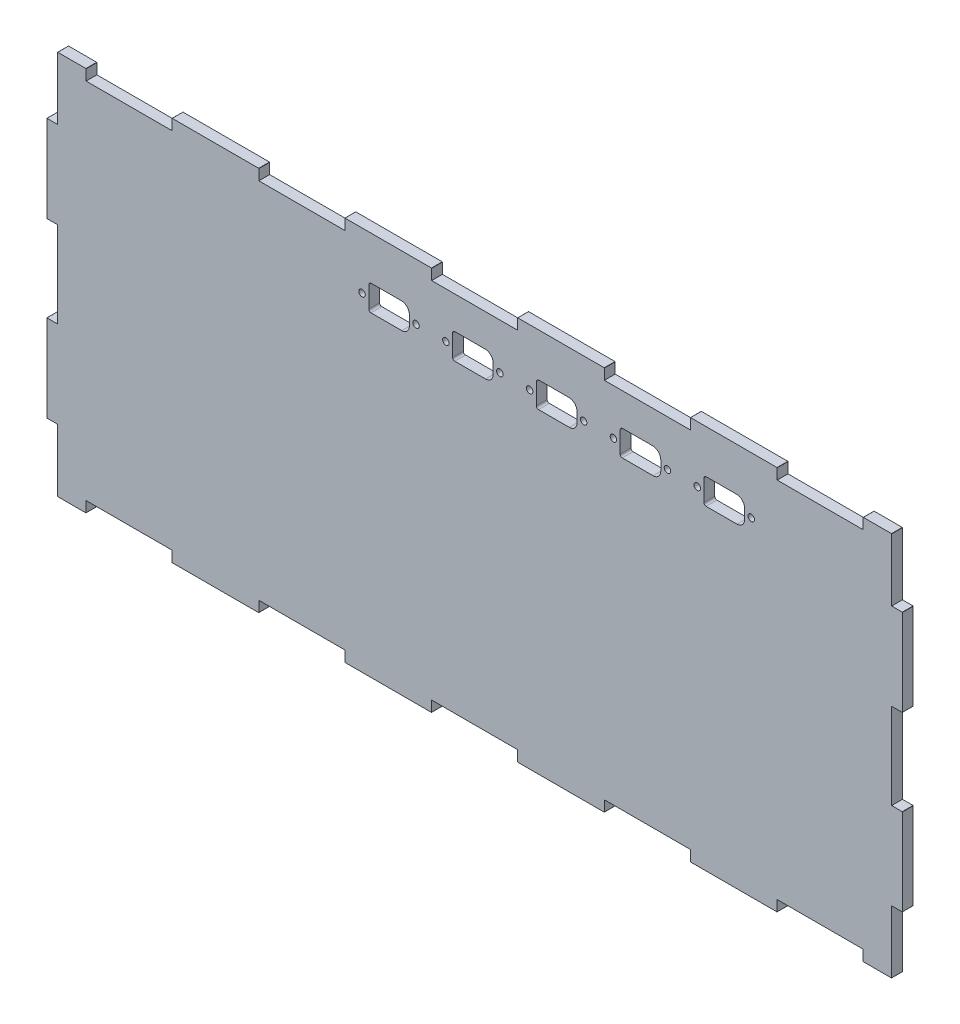
SolidWorks part; units mm, degrees
material "Acrylic (Medium-high impact)"
ref_plane "Front Plane" through (0, 0, 0) normal (0, 0, 1) x (1, 0, 0)
ref_plane "Top Plane" through (0, 0, 0) normal (0, 1, 0) x (1, 0, 0)
ref_plane "Right Plane" through (0, 0, 0) normal (1, 0, 0) x (0, 0, -1)
sketch "Model" plane through (0, 0, 0) normal (0, 0, 1) x (1, 0, 0)
  line L0 (-179.94, -89.08) -> (-179.93, -89.07)
  line L1 (-179.93, -89.07) -> (-179.92, -89.05)
  line L2 (-179.92, -89.05) -> (-179.91, -89.04)
  line L3 (-179.91, -89.04) -> (-179.9, -89.02)
  line L4 (-179.9, -89.02) -> (-179.9, -84.1)
  line L5 (-179.9, -84.1) -> (-140.1, -84.1)
  line L6 (-140.1, -84.1) -> (-140.1, -89.02)
  line L7 (-140.1, -89.02) -> (-140.08, -89.06)
  line L8 (-140.08, -89.06) -> (-140.07, -89.07)
  line L9 (-140.07, -89.07) -> (-140.05, -89.08)
  line L10 (-140.05, -89.08) -> (-140.04, -89.09)
  line L11 (-140.04, -89.09) -> (-140.02, -89.1)
  line L12 (-140.02, -89.1) -> (-99.98, -89.1)
  line L13 (-99.98, -89.1) -> (-99.94, -89.08)
  line L14 (-99.94, -89.08) -> (-99.93, -89.07)
  line L15 (-99.93, -89.07) -> (-99.92, -89.05)
  line L16 (-99.92, -89.05) -> (-99.91, -89.04)
  line L17 (-99.91, -89.04) -> (-99.9, -89.02)
  line L18 (-99.9, -89.02) -> (-99.9, -84.1)
  line L19 (-99.9, -84.1) -> (-60.1, -84.1)
  line L20 (-60.1, -84.1) -> (-60.1, -89.02)
  line L21 (-60.1, -89.02) -> (-60.08, -89.06)
  line L22 (-60.08, -89.06) -> (-60.07, -89.07)
  line L23 (-60.07, -89.07) -> (-60.05, -89.08)
  line L24 (-60.05, -89.08) -> (-60.04, -89.09)
  line L25 (-60.04, -89.09) -> (-60.02, -89.1)
  line L26 (-60.02, -89.1) -> (-19.98, -89.1)
  line L27 (-19.98, -89.1) -> (-19.94, -89.08)
  line L28 (-19.94, -89.08) -> (-19.93, -89.07)
  line L29 (-19.93, -89.07) -> (-19.92, -89.05)
  line L30 (-19.92, -89.05) -> (-19.91, -89.04)
  line L31 (-19.91, -89.04) -> (-19.9, -89.02)
  line L32 (-19.9, -89.02) -> (-19.9, -84.1)
  line L33 (-19.9, -84.1) -> (19.9, -84.1)
  line L34 (19.9, -84.1) -> (19.9, -89.02)
  line L35 (19.9, -89.02) -> (19.92, -89.06)
  line L36 (19.92, -89.06) -> (19.93, -89.07)
  line L37 (19.93, -89.07) -> (19.95, -89.08)
  line L38 (19.95, -89.08) -> (19.96, -89.09)
  line L39 (19.96, -89.09) -> (19.98, -89.1)
  line L40 (19.98, -89.1) -> (60.02, -89.1)
  line L41 (60.02, -89.1) -> (60.06, -89.08)
  line L42 (60.06, -89.08) -> (60.07, -89.07)
  line L43 (60.07, -89.07) -> (60.08, -89.05)
  line L44 (60.08, -89.05) -> (60.09, -89.04)
  line L45 (60.09, -89.04) -> (60.1, -89.02)
  line L46 (60.1, -89.02) -> (60.1, -84.1)
  line L47 (60.1, -84.1) -> (99.9, -84.1)
  line L48 (99.9, -84.1) -> (99.9, -89.02)
  line L49 (99.9, -89.02) -> (99.92, -89.06)
  line L50 (99.92, -89.06) -> (99.93, -89.07)
  line L51 (99.93, -89.07) -> (99.95, -89.08)
  line L52 (99.95, -89.08) -> (99.96, -89.09)
  line L53 (99.96, -89.09) -> (99.98, -89.1)
  line L54 (99.98, -89.1) -> (140.02, -89.1)
  line L55 (140.02, -89.1) -> (140.06, -89.08)
  line L56 (140.06, -89.08) -> (140.07, -89.07)
  line L57 (140.07, -89.07) -> (140.08, -89.05)
  line L58 (140.08, -89.05) -> (140.09, -89.04)
  line L59 (140.09, -89.04) -> (140.1, -89.02)
  line L60 (140.1, -89.02) -> (140.1, -84.1)
  line L61 (140.1, -84.1) -> (179.9, -84.1)
  line L62 (179.9, -84.1) -> (179.9, -89.02)
  line L63 (179.9, -89.02) -> (179.92, -89.06)
  line L64 (179.92, -89.06) -> (179.93, -89.07)
  line L65 (179.93, -89.07) -> (179.95, -89.08)
  line L66 (179.95, -89.08) -> (179.96, -89.09)
  line L67 (179.96, -89.09) -> (179.98, -89.1)
  line L68 (179.98, -89.1) -> (193.02, -89.1)
  line L69 (193.02, -89.1) -> (193.06, -89.08)
  line L70 (193.06, -89.08) -> (193.07, -89.07)
  line L71 (193.07, -89.07) -> (193.08, -89.05)
  line L72 (193.08, -89.05) -> (193.09, -89.04)
  line L73 (193.09, -89.04) -> (193.1, -89.02)
  line L74 (193.1, -89.02) -> (193.1, -60.1)
  line L75 (193.1, -60.1) -> (198.02, -60.1)
  line L76 (198.02, -60.1) -> (198.06, -60.08)
  line L77 (198.06, -60.08) -> (198.07, -60.07)
  line L78 (198.07, -60.07) -> (198.08, -60.05)
  line L79 (198.08, -60.05) -> (198.09, -60.04)
  line L80 (198.09, -60.04) -> (198.1, -60.02)
  line L81 (198.1, -60.02) -> (198.1, -19.98)
  line L82 (198.1, -19.98) -> (198.08, -19.94)
  line L83 (198.08, -19.94) -> (198.07, -19.93)
  line L84 (198.07, -19.93) -> (198.05, -19.92)
  line L85 (198.05, -19.92) -> (198.04, -19.91)
  line L86 (198.04, -19.91) -> (198.02, -19.9)
  line L87 (198.02, -19.9) -> (193.1, -19.9)
  line L88 (193.1, -19.9) -> (193.1, 19.9)
  line L89 (193.1, 19.9) -> (198.02, 19.9)
  line L90 (198.02, 19.9) -> (198.06, 19.92)
  line L91 (198.06, 19.92) -> (198.07, 19.93)
  line L92 (198.07, 19.93) -> (198.08, 19.95)
  line L93 (198.08, 19.95) -> (198.09, 19.96)
  line L94 (198.09, 19.96) -> (198.1, 19.98)
  line L95 (198.1, 19.98) -> (198.1, 60.02)
  line L96 (198.1, 60.02) -> (198.08, 60.06)
  line L97 (198.08, 60.06) -> (198.07, 60.07)
  line L98 (198.07, 60.07) -> (198.05, 60.08)
  line L99 (198.05, 60.08) -> (198.04, 60.09)
  line L100 (198.04, 60.09) -> (198.02, 60.1)
  line L101 (198.02, 60.1) -> (193.1, 60.1)
  line L102 (193.1, 60.1) -> (193.1, 89.02)
  line L103 (193.1, 89.02) -> (193.08, 89.06)
  line L104 (193.08, 89.06) -> (193.07, 89.07)
  line L105 (193.07, 89.07) -> (193.05, 89.08)
  line L106 (193.05, 89.08) -> (193.04, 89.09)
  line L107 (193.04, 89.09) -> (193.02, 89.1)
  line L108 (193.02, 89.1) -> (179.98, 89.1)
  line L109 (179.98, 89.1) -> (179.94, 89.08)
  line L110 (179.94, 89.08) -> (179.93, 89.07)
  line L111 (179.93, 89.07) -> (179.92, 89.05)
  line L112 (179.92, 89.05) -> (179.91, 89.04)
  line L113 (179.91, 89.04) -> (179.9, 89.02)
  line L114 (179.9, 89.02) -> (179.9, 84.1)
  line L115 (179.9, 84.1) -> (140.1, 84.1)
  line L116 (140.1, 84.1) -> (140.1, 89.02)
  line L117 (140.1, 89.02) -> (140.08, 89.06)
  line L118 (140.08, 89.06) -> (140.07, 89.07)
  line L119 (140.07, 89.07) -> (140.05, 89.08)
  line L120 (140.05, 89.08) -> (140.04, 89.09)
  line L121 (140.04, 89.09) -> (140.02, 89.1)
  line L122 (140.02, 89.1) -> (99.98, 89.1)
  line L123 (99.98, 89.1) -> (99.94, 89.08)
  line L124 (99.94, 89.08) -> (99.93, 89.07)
  line L125 (99.93, 89.07) -> (99.92, 89.05)
  line L126 (99.92, 89.05) -> (99.91, 89.04)
  line L127 (99.91, 89.04) -> (99.9, 89.02)
  line L128 (99.9, 89.02) -> (99.9, 84.1)
  line L129 (99.9, 84.1) -> (60.1, 84.1)
  line L130 (60.1, 84.1) -> (60.1, 89.02)
  line L131 (60.1, 89.02) -> (60.08, 89.06)
  line L132 (60.08, 89.06) -> (60.07, 89.07)
  line L133 (60.07, 89.07) -> (60.05, 89.08)
  line L134 (60.05, 89.08) -> (60.04, 89.09)
  line L135 (60.04, 89.09) -> (60.02, 89.1)
  line L136 (60.02, 89.1) -> (19.98, 89.1)
  line L137 (19.98, 89.1) -> (19.94, 89.08)
  line L138 (19.94, 89.08) -> (19.93, 89.07)
  line L139 (19.93, 89.07) -> (19.92, 89.05)
  line L140 (19.92, 89.05) -> (19.91, 89.04)
  line L141 (19.91, 89.04) -> (19.9, 89.02)
  line L142 (19.9, 89.02) -> (19.9, 84.1)
  line L143 (19.9, 84.1) -> (-19.9, 84.1)
  line L144 (-19.9, 84.1) -> (-19.9, 89.02)
  line L145 (-19.9, 89.02) -> (-19.92, 89.06)
  line L146 (-19.92, 89.06) -> (-19.93, 89.07)
  line L147 (-19.93, 89.07) -> (-19.95, 89.08)
  line L148 (-19.95, 89.08) -> (-19.96, 89.09)
  line L149 (-19.96, 89.09) -> (-19.98, 89.1)
  line L150 (-19.98, 89.1) -> (-60.02, 89.1)
  line L151 (-60.02, 89.1) -> (-60.06, 89.08)
  line L152 (-60.06, 89.08) -> (-60.07, 89.07)
  line L153 (-60.07, 89.07) -> (-60.08, 89.05)
  line L154 (-60.08, 89.05) -> (-60.09, 89.04)
  line L155 (-60.09, 89.04) -> (-60.1, 89.02)
  line L156 (-60.1, 89.02) -> (-60.1, 84.1)
  line L157 (-60.1, 84.1) -> (-99.9, 84.1)
  line L158 (-99.9, 84.1) -> (-99.9, 89.02)
  line L159 (-99.9, 89.02) -> (-99.92, 89.06)
  line L160 (-99.92, 89.06) -> (-99.93, 89.07)
  line L161 (-99.93, 89.07) -> (-99.95, 89.08)
  line L162 (-99.95, 89.08) -> (-99.96, 89.09)
  line L163 (-99.96, 89.09) -> (-99.98, 89.1)
  line L164 (-99.98, 89.1) -> (-140.02, 89.1)
  line L165 (-140.02, 89.1) -> (-140.06, 89.08)
  line L166 (-140.06, 89.08) -> (-140.07, 89.07)
  line L167 (-140.07, 89.07) -> (-140.08, 89.05)
  line L168 (-140.08, 89.05) -> (-140.09, 89.04)
  line L169 (-140.09, 89.04) -> (-140.1, 89.02)
  line L170 (-140.1, 89.02) -> (-140.1, 84.1)
  line L171 (-140.1, 84.1) -> (-179.9, 84.1)
  line L172 (-179.9, 84.1) -> (-179.9, 89.02)
  line L173 (-179.9, 89.02) -> (-179.92, 89.06)
  line L174 (-179.92, 89.06) -> (-179.93, 89.07)
  line L175 (-179.93, 89.07) -> (-179.95, 89.08)
  line L176 (-179.95, 89.08) -> (-179.96, 89.09)
  line L177 (-179.96, 89.09) -> (-179.98, 89.1)
  line L178 (-179.98, 89.1) -> (-193.02, 89.1)
  line L179 (-193.02, 89.1) -> (-193.06, 89.08)
  line L180 (-193.06, 89.08) -> (-193.07, 89.07)
  line L181 (-193.07, 89.07) -> (-193.08, 89.05)
  line L182 (-193.08, 89.05) -> (-193.09, 89.04)
  line L183 (-193.09, 89.04) -> (-193.1, 89.02)
  line L184 (-193.1, 89.02) -> (-193.1, 60.1)
  line L185 (-193.1, 60.1) -> (-198.02, 60.1)
  line L186 (-198.02, 60.1) -> (-198.06, 60.08)
  line L187 (-198.06, 60.08) -> (-198.07, 60.07)
  line L188 (-198.07, 60.07) -> (-198.08, 60.05)
  line L189 (-198.08, 60.05) -> (-198.09, 60.04)
  line L190 (-198.09, 60.04) -> (-198.1, 60.02)
  line L191 (-198.1, 60.02) -> (-198.1, 19.98)
  line L192 (-198.1, 19.98) -> (-198.08, 19.94)
  line L193 (-198.08, 19.94) -> (-198.07, 19.93)
  line L194 (-198.07, 19.93) -> (-198.05, 19.92)
  line L195 (-198.05, 19.92) -> (-198.04, 19.91)
  line L196 (-198.04, 19.91) -> (-198.02, 19.9)
  line L197 (-198.02, 19.9) -> (-193.1, 19.9)
  line L198 (-193.1, 19.9) -> (-193.1, -19.9)
  line L199 (-193.1, -19.9) -> (-198.02, -19.9)
  line L200 (-198.02, -19.9) -> (-198.06, -19.92)
  line L201 (-198.06, -19.92) -> (-198.07, -19.93)
  line L202 (-198.07, -19.93) -> (-198.08, -19.95)
  line L203 (-198.08, -19.95) -> (-198.09, -19.96)
  line L204 (-198.09, -19.96) -> (-198.1, -19.98)
  line L205 (-198.1, -19.98) -> (-198.1, -60.02)
  line L206 (-198.1, -60.02) -> (-198.08, -60.06)
  line L207 (-198.08, -60.06) -> (-198.07, -60.07)
  line L208 (-198.07, -60.07) -> (-198.05, -60.08)
  line L209 (-198.05, -60.08) -> (-198.04, -60.09)
  line L210 (-198.04, -60.09) -> (-198.02, -60.1)
  line L211 (-198.02, -60.1) -> (-193.1, -60.1)
  line L212 (-193.1, -60.1) -> (-193.1, -89.02)
  line L213 (-193.1, -89.02) -> (-193.08, -89.06)
  line L214 (-193.08, -89.06) -> (-193.07, -89.07)
  line L215 (-193.07, -89.07) -> (-193.05, -89.08)
  line L216 (-193.05, -89.08) -> (-193.04, -89.09)
  line L217 (-193.04, -89.09) -> (-193.02, -89.1)
  line L218 (-193.02, -89.1) -> (-179.98, -89.1)
  line L219 (-179.98, -89.1) -> (-179.94, -89.08)
extrude "Boss-Extrude1" add sketch "Model" along normal blind 5
sketch "Sketch2" plane through (0, 0, 5) normal (0, 0, 1) x (1, 0, 0)
  line L0 (-30.2088, 62.97) -> (-10.2088, 62.97) construction
  line L1 (-33.7338, 57.12) -> (-48.0088, 57.12)
  line L2 (-47.8088, 69.02) -> (-33.9338, 69.02)
  line L3 (-49.0088, 58.12) -> (-49.0088, 67.82)
  line L4 (-30.2088, 60.645) -> (-30.2088, 65.295)
  line L5 (5.0662, 57.12) -> (-9.2088, 57.12)
  line L6 (-9.0088, 69.02) -> (4.8662, 69.02)
  line L7 (-10.2088, 58.12) -> (-10.2088, 67.82)
  line L8 (8.5912, 60.645) -> (8.5912, 65.295)
  line L9 (43.8662, 57.12) -> (29.5912, 57.12)
  line L10 (29.7912, 69.02) -> (43.6662, 69.02)
  line L11 (28.5912, 58.12) -> (28.5912, 67.82)
  line L12 (47.3912, 60.645) -> (47.3912, 65.295)
  line L13 (82.6662, 57.12) -> (68.3912, 57.12)
  line L14 (68.5912, 69.02) -> (82.4662, 69.02)
  line L15 (67.3912, 58.12) -> (67.3912, 67.82)
  line L16 (86.1912, 60.645) -> (86.1912, 65.295)
  line L17 (8.5912, 62.97) -> (28.5912, 62.97) construction
  line L18 (47.3912, 62.97) -> (67.3912, 62.97) construction
  line L19 (121.4662, 57.12) -> (107.1912, 57.12)
  line L20 (107.3912, 69.02) -> (121.2662, 69.02)
  line L21 (106.1912, 58.12) -> (106.1912, 67.82)
  line L22 (124.9912, 60.645) -> (124.9912, 65.295)
  line L23 (86.1912, 62.97) -> (106.1912, 62.97) construction
  line L24 (-52.1088, 62.97) -> (-49.0088, 62.97) construction
  line L25 (-13.3088, 62.97) -> (-10.2088, 62.97) construction
  line L26 (25.4912, 62.97) -> (28.5912, 62.97) construction
  line L27 (64.2912, 62.97) -> (67.3912, 62.97) construction
  line L28 (103.0912, 62.97) -> (106.1912, 62.97) construction
  line L29 (128.0912, 62.97) -> (193.1, 62.97) construction
  line L30 (193.1, 62.97) -> (193.1, 89.02) construction
  arc A0 (-30.2088, 60.645) -> (-33.7338, 57.12) centre (-33.7338, 60.645) cw
  arc A1 (-30.2088, 65.295) -> (-33.9338, 69.02) centre (-33.9338, 65.295) ccw
  arc A2 (-48.0088, 57.12) -> (-49.0088, 58.12) centre (-48.0088, 58.12) cw
  arc A3 (-49.0088, 67.82) -> (-47.8088, 69.02) centre (-47.8088, 67.82) cw
  arc A4 (8.5912, 60.645) -> (5.0662, 57.12) centre (5.0662, 60.645) cw
  arc A5 (8.5912, 65.295) -> (4.8662, 69.02) centre (4.8662, 65.295) ccw
  arc A6 (-9.2088, 57.12) -> (-10.2088, 58.12) centre (-9.2088, 58.12) cw
  arc A7 (-10.2088, 67.82) -> (-9.0088, 69.02) centre (-9.0088, 67.82) cw
  arc A8 (47.3912, 60.645) -> (43.8662, 57.12) centre (43.8662, 60.645) cw
  arc A9 (47.3912, 65.295) -> (43.6662, 69.02) centre (43.6662, 65.295) ccw
  arc A10 (29.5912, 57.12) -> (28.5912, 58.12) centre (29.5912, 58.12) cw
  arc A11 (28.5912, 67.82) -> (29.7912, 69.02) centre (29.7912, 67.82) cw
  arc A12 (86.1912, 60.645) -> (82.6662, 57.12) centre (82.6662, 60.645) cw
  arc A13 (86.1912, 65.295) -> (82.4662, 69.02) centre (82.4662, 65.295) ccw
  arc A14 (68.3912, 57.12) -> (67.3912, 58.12) centre (68.3912, 58.12) cw
  arc A15 (67.3912, 67.82) -> (68.5912, 69.02) centre (68.5912, 67.82) cw
  arc A16 (124.9912, 60.645) -> (121.4662, 57.12) centre (121.4662, 60.645) cw
  arc A17 (124.9912, 65.295) -> (121.2662, 69.02) centre (121.2662, 65.295) ccw
  arc A18 (107.1912, 57.12) -> (106.1912, 58.12) centre (107.1912, 58.12) cw
  arc A19 (106.1912, 67.82) -> (107.3912, 69.02) centre (107.3912, 67.82) cw
  circle A20 centre (-52.1088, 62.97) radius 1.5
  circle A21 centre (-27.1088, 62.97) radius 1.5
  circle A22 centre (-13.3088, 62.97) radius 1.5
  circle A23 centre (11.6912, 62.97) radius 1.5
  circle A24 centre (25.4912, 62.97) radius 1.5
  circle A25 centre (50.4912, 62.97) radius 1.5
  circle A26 centre (64.2912, 62.97) radius 1.5
  circle A27 centre (89.2912, 62.97) radius 1.5
  circle A28 centre (103.0912, 62.97) radius 1.5
  circle A29 centre (128.0912, 62.97) radius 1.5
  dimension "D5" = 3
  dimension "D6" = 3
  dimension "D1" = 20
  dimension "D2" = 20
  dimension "D3" = 20
  dimension "D4" = 20
  dimension "D7" = 25
extrude "Cut-Extrude1" cut sketch "Sketch2" against normal through all
